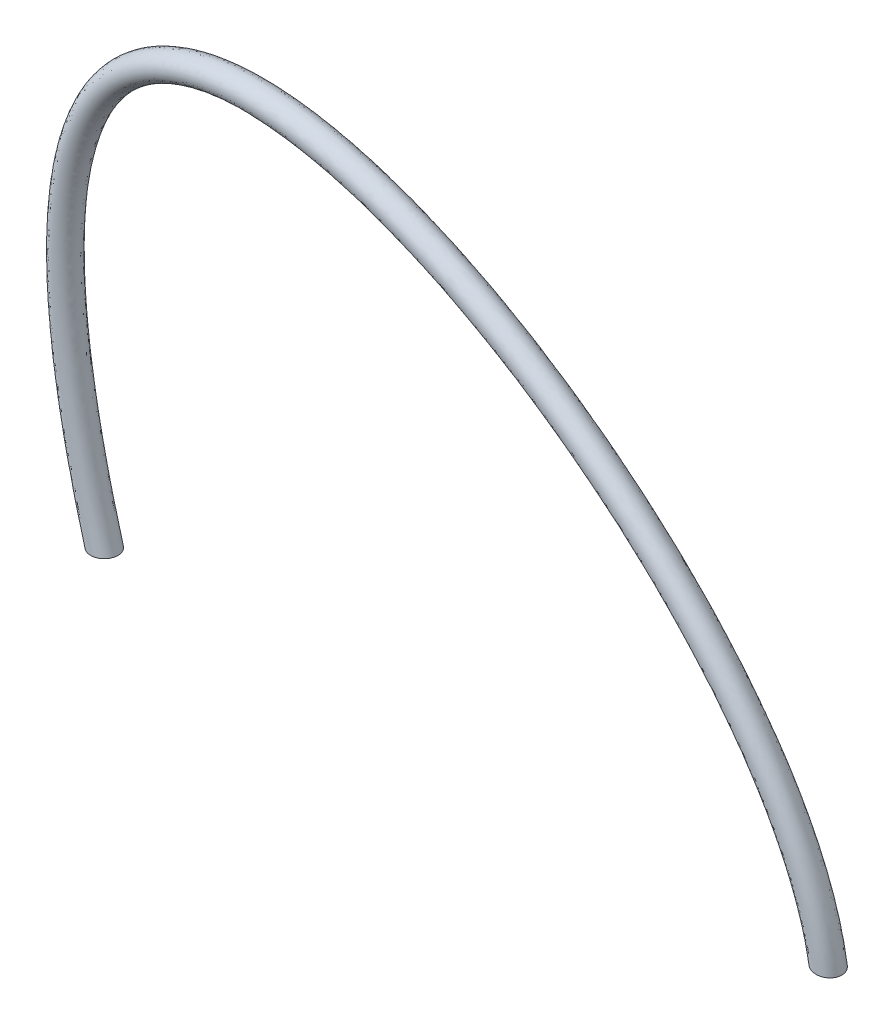
SolidWorks part; units mm, degrees
material "AISI 1020"
ref_plane "Front" through (0, 0, 0) normal (0, 0, 1) x (1, 0, 0)
ref_plane "Top" through (0, 0, 0) normal (0, 1, 0) x (1, 0, 0)
ref_plane "Right" through (0, 0, 0) normal (1, 0, 0) x (0, 0, -1)
sketch "Sketch2" plane through (0, 0, 0) normal (0, 0, 1) x (1, 0, 0)
  spline S0 degree 3 poles (0, 0) (-17.1655, 61.2561) (48.7786, 26.9403) (53.0791, 0) knots 0 0 0 0 1 1 1 1
  point P2 (0, 0)
  point P4 (0, 0)
  point P6 (-0.4773, 1.7651)
  point P7 (0, 0)
  point P9 (0, 0)
  point P10 (0, 0)
  point P11 (0, 0)
  point P12 (0, 0)
  point P13 (0, 0)
  dimension "D1" = 100
  dimension "D3" = 33.9658
  dimension "D2" = 53.0791
  dimension "D4" = 56.6096
  dimension "D5" = 19.395
ref_plane "Plane1" through (0, 0, 0) normal (0, 1, 0) x (1, 0, 0)
sketch "Sketch3" plane through (0, 0, 0) normal (0, 1, 0) x (1, 0, 0)
  circle A0 centre (0, 0) radius 1
  dimension "D1" = 2
sweep "Sweep1" add profiles "Sketch3" path "Sketch2"
